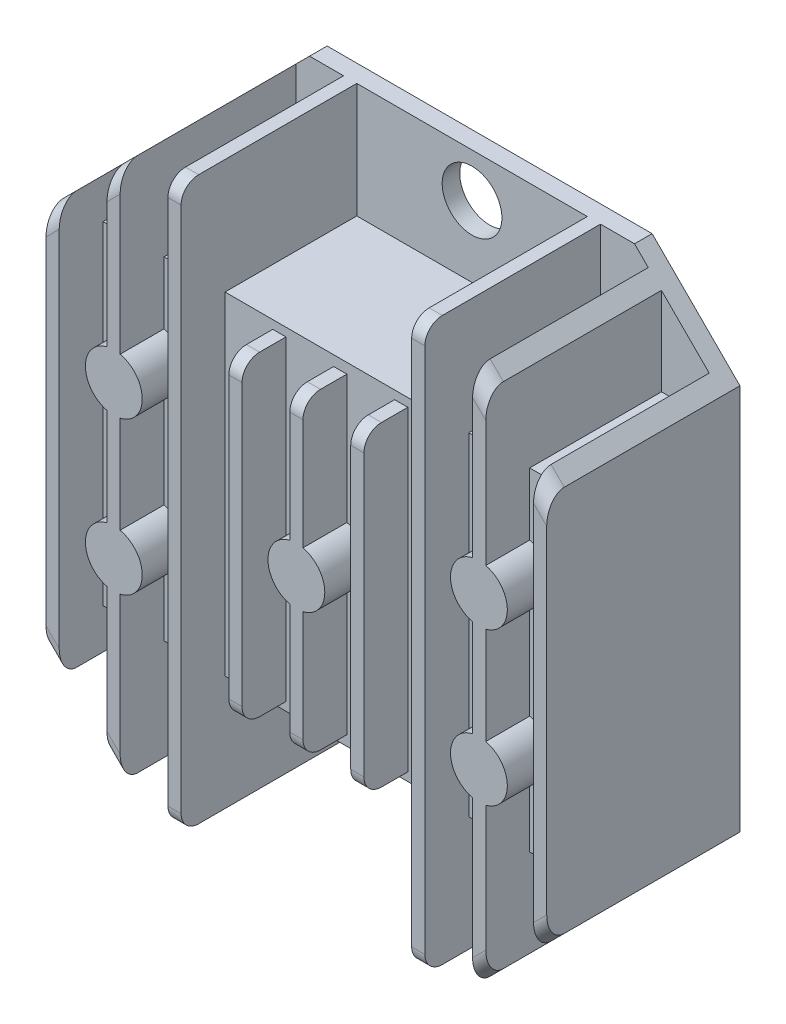
SolidWorks part; units mm, degrees
ref_plane "Ebene vorne" through (0, 0, 0) normal (1, 0, 0) x (0, 1, 0)
ref_plane "Ebene oben" through (0, 0, 0) normal (0, 0, 1) x (0, 1, 0)
ref_plane "Ebene rechts" through (0, 0, 0) normal (0, 1, 0) x (-1, 0, 0)
sketch "Skizze1" plane through (0, 0, 0) normal (0, 0, 1) x (0, 1, 0)
  line L0 (0, 48.454) -> (0, -48.454) construction
  line L5 (22, 28.5) -> (32, 18.5)
  line L7 (0, -28.5) -> (22, -28.5)
  line L8 (0, -28.5) -> (0, 28.5)
  line L9 (0, 28.5) -> (22, 28.5)
  line L10 (32, -18.5) -> (32, 18.5)
  line L11 (22, -28.5) -> (32, -18.5)
  line L12 (32, 0) -> (27, 0) construction
  circle A0 centre (27, 0) radius 3.4
  point P3 (0, 0)
  point P5 (32, 28.5)
  point P9 (32, -28.5)
  point P16 (28.4026, -3.4725)
  dimension "D4" = 6.8
  dimension "D1" = 64
  dimension "D2" = 57
  dimension "D3" = 5
extrude "Aufsatz-Linear austragen1" add sketch "Skizze1" along normal blind 2
sketch "Skizze2" plane through (0, 0, 2) normal (0, 0, 1) x (1, 0, 0)
  line L0 (-28.5, 22) -> (-28.5, 0) construction
  line L1 (-28.5, 18.9328) -> (28.5, 18.9328)
  line L2 (-28.5, 18.9328) -> (-28.5, 0)
  line L3 (-28.5, 0) -> (28.5, 0)
  line L4 (28.5, 18.9328) -> (28.5, 0)
extrude "Aufsatz-Linear austragen2" add sketch "Skizze2" along normal blind 15
sketch "Skizze3" plane through (0, 0, 17) normal (0, 0, 1) x (1, 0, 0)
  line L1 (0, 0) -> (-34.6234, 0)
  line L2 (0, 0) -> (0, 45.1108)
  line L3 (0, 45.1108) -> (-34.6234, 45.1108)
  line L4 (-34.6234, 0) -> (-34.6234, 45.1108)
extrude "Schnitt-Linear austragen1" cut sketch "Skizze3" against normal through all both and the other way through all
sketch "Skizze4" plane through (0, 0, 17) normal (0, 0, 1) x (1, 0, 0)
  line L0 (0, 0) -> (28.5, 0) construction
  line L1 (13.125, 0) -> (14.625, 0)
  line L2 (13.125, 0) -> (13.125, 32)
  line L3 (13.125, 32) -> (14.625, 32)
  line L4 (14.625, 0) -> (14.625, 32)
  line L5 (18.5, 32) -> (0, 32) construction
  line L6 (27, 23.5) -> (28.5, 22)
  line L7 (20.0625, 0) -> (21.5625, 0)
  line L8 (20.0625, 0) -> (20.0625, 30.4375)
  line L10 (21.5625, 0) -> (21.5625, 28.9375)
  line L11 (28.5, 0) -> (27, 0)
  line L12 (28.5, 0) -> (28.5, 22)
  line L14 (27, 0) -> (27, 23.5)
  line L16 (28.5, 22) -> (18.5, 32) construction
  line L17 (0, 0) -> (0, 18.9328) construction
  line L18 (6.1875, 17.9729) -> (7.6875, 17.9729)
  line L19 (6.1875, 17.9729) -> (6.1875, 0)
  line L20 (6.1875, 0) -> (7.6875, 0)
  line L21 (7.6875, 17.9729) -> (7.6875, 0)
  line L22 (0, 17.7756) -> (0.75, 17.7756)
  line L23 (0, 17.7756) -> (0, 0)
  line L24 (0, 0) -> (0.75, 0)
  line L25 (0.75, 17.7756) -> (0.75, 0)
  line L26 (0.75, 5.8395) -> (6.1875, 5.8395) construction
  line L27 (7.6875, 5.8395) -> (13.125, 5.8395) construction
  line L28 (14.625, 5.8395) -> (20.0625, 5.8395) construction
  line L29 (21.5625, 5.8395) -> (27, 5.8395) construction
  line L30 (20.0625, 30.4375) -> (21.5625, 28.9375)
  point P9 (21.5625, 0)
  dimension "D1" = 1.5
  dimension "D2" = 0.75
extrude "Aufsatz-Linear austragen3" add sketch "Skizze4" against normal up to surface (15 mm away) and the other way blind 5 up to face at (11.2714, 25.4094, 2)
fillet "Verrundung1" radius 2 5 edges at (0.375, 17.7756, 22) (6.9375, 17.9729, 22) (27.75, 22.75, 22) (20.8125, 29.6875, 22) (13.875, 32, 22)
sketch "Skizze5" plane through (0, 0, 22) normal (0, 0, 1) x (1, 0, 0)
  circle A0 centre (20.7826, 8.6781) radius 3.2346
extrude "Aufsatz-Linear austragen4" add sketch "Skizze5" against normal up to surface (5 mm away) up to face at (24.2812, 9.4664, 17)
sketch "Skizze6" plane through (0, 0, 17) normal (0, 0, 1) x (1, 0, 0)
  line L0 (3.2346, 0) -> (0, 0)
  line L2 (0, 0) -> (0, 3.2346)
  arc A0 (3.2346, 0) -> (0, 3.2346) centre (0, 0) ccw
  arc A2 (20.0625, 11.8315) -> (20.0625, 5.5247) centre (20.7826, 8.6781) ccw construction
  line M2 (0.75, 0) -> (6.1875, 0)
  line M11 (0.75, 17.7756) -> (0.75, 0)
extrude "Aufsatz-Linear austragen7" add sketch "Skizze6" along normal up to surface (5 mm away) contours A0 M2 M11 | A0 L2 L0 M11 region at (1.7861, 1.2777, 17) region at (0.3733, 1.6028, 17) up to face at (0.375, 7.8878, 22)
mirror "Spiegeln1" about plane through (28.5, 0, 2) normal (0, 1, 0) of bodies 106
mirror "Spiegeln2" about plane through (0, 0, 0) normal (1, 0, 0) of bodies 107
sketch "Skizze7" plane through (-28.5, 0, 0) normal (-1, 0, 0) x (0, -1, 0)
  circle A0 centre (-3, 2.8859) radius 1.5
  circle A1 centre (0, 2.8859) radius 1.5
  circle A2 centre (3, 2.8859) radius 1.5
  point P6 (0, 0)
  point P7 (0, 0)
  point P9 (-0.2304, 4.3764)
  dimension "D1" = 3
extrude "Aufsatz-Linear austragen9" add sketch "Skizze7" along normal blind 11 separate body contours A0 | A1 | A2 region at (-28.5, 3, 2.8859) region at (-28.5, -3, 2.8859) region at (-28.5, 0, 2.8859)
